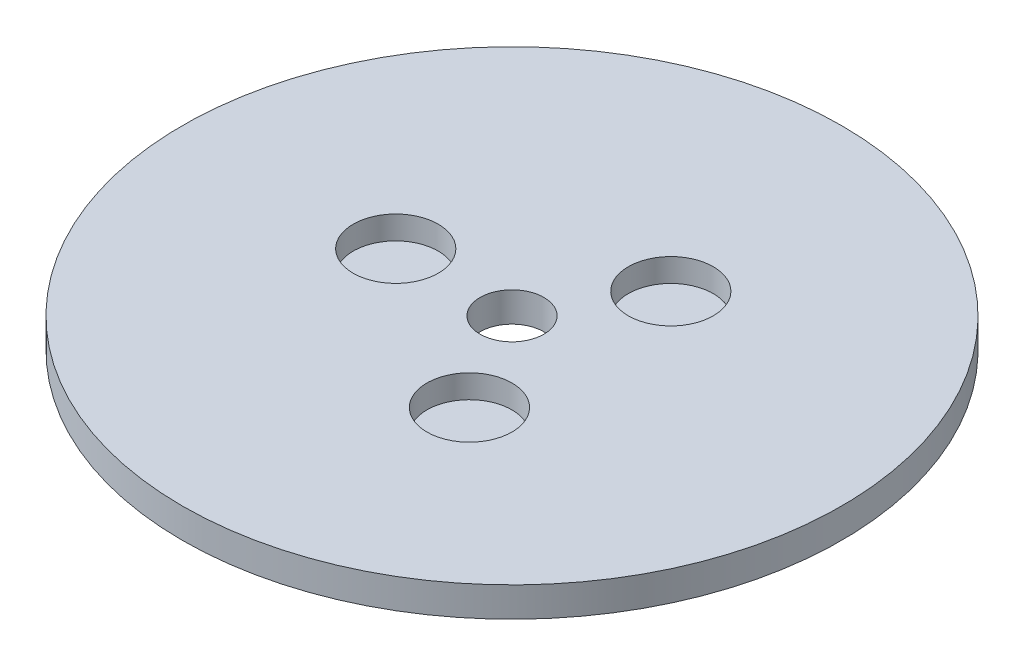
SolidWorks part; units mm, degrees
ref_plane "Front Plane" through (0, 0, 0) normal (0, 0, 1) x (1, 0, 0)
ref_plane "Top Plane" through (0, 0, 0) normal (0, 1, 0) x (1, 0, 0)
ref_plane "Right Plane" through (0, 0, 0) normal (1, 0, 0) x (0, 0, -1)
sketch "Sketch1" plane through (0, 0, 0) normal (0, 1, 0) x (1, 0, 0)
  circle A0 centre (0, 0) radius 77.5
  dimension "FLANGE_OD" = 155
extrude "Boss-Extrude1" add sketch "Sketch1" along normal blind 7
sketch "Sketch2" plane through (0, 0, 0) normal (0, 1, 0) x (1, 0, 0)
  circle A0 centre (0, 0) radius 7.5
  dimension "BORE_D" = 15
extrude "Cut-Extrude1" cut sketch "Sketch2" along normal through all
sketch "Sketch3" plane through (0, 7, 0) normal (0, 1, 0) x (1, 0, 0)
  circle A0 centre (0, 0) radius 27.3398 construction
  circle A1 centre (-27.3398, 0) radius 10
  dimension "BOLT_D" = 20
  dimension "BOLT_PCD" = 54.6796
extrude "Cut-Extrude2" cut sketch "Sketch3" against normal blind 5.4826
pattern_circular "CirPattern1" count 3 over 360 about axis through (0, 0, 0) along (0, 1, 0) of "Cut-Extrude2"
